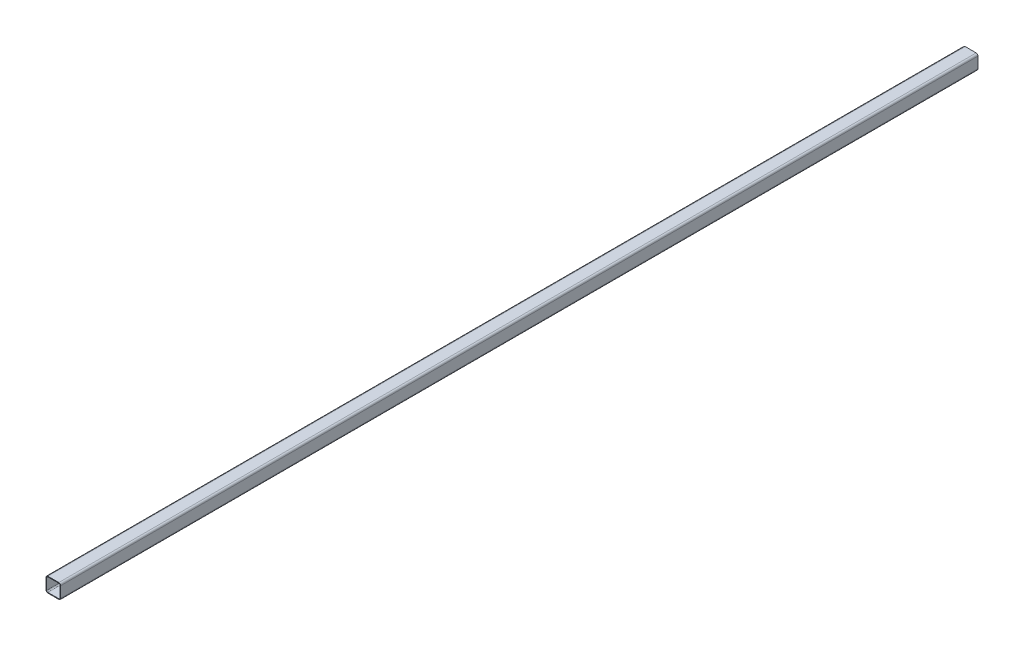
SolidWorks part; units mm, degrees
material "AISI 1010 Steel, hot rolled bar"
ref_plane "Front Plane" through (0, 0, 0) normal (0, 0, 1) x (1, 0, 0)
ref_plane "Top Plane" through (0, 0, 0) normal (0, 1, 0) x (1, 0, 0)
ref_plane "Right Plane" through (0, 0, 0) normal (1, 0, 0) x (0, 0, -1)
sketch "Sketch1" plane through (0, 0, 0) normal (0, 0, 1) x (1, 0, 0)
  line L0 (-6, 7.32) -> (6, 7.32)
  line L1 (-6, -8) -> (6, -8)
  line L2 (-8, -6) -> (-8, 6)
  line L3 (-6, 8) -> (6, 8)
  line L4 (8, -6) -> (8, 6)
  line L5 (-8, -8) -> (8, 8) construction
  line L6 (-8, 8) -> (8, -8) construction
  line L7 (7.32, -6) -> (7.32, 6)
  line L8 (-6, -7.32) -> (6, -7.32)
  line L9 (-7.32, -6) -> (-7.32, 6)
  arc A0 (-6, -8) -> (-8, -6) centre (-6, -6) cw
  arc A1 (6, -8) -> (8, -6) centre (6, -6) ccw
  arc A2 (6, 8) -> (8, 6) centre (6, 6) cw
  arc A3 (-8, 6) -> (-6, 8) centre (-6, 6) cw
  arc A4 (6, 7.32) -> (7.32, 6) centre (6, 6) cw
  arc A5 (6, -7.32) -> (7.32, -6) centre (6, -6) ccw
  arc A6 (-6, -7.32) -> (-7.32, -6) centre (-6, -6) cw
  arc A7 (-7.32, 6) -> (-6, 7.32) centre (-6, 6) cw
  point P0 (0, 0)
  dimension "D3" = 2
  dimension "D1" = 16
  dimension "D2" = 16
  dimension "D4" = 0.68
extrude "Boss-Extrude1" add sketch "Sketch1" along normal blind 500 and the other way blind 500
